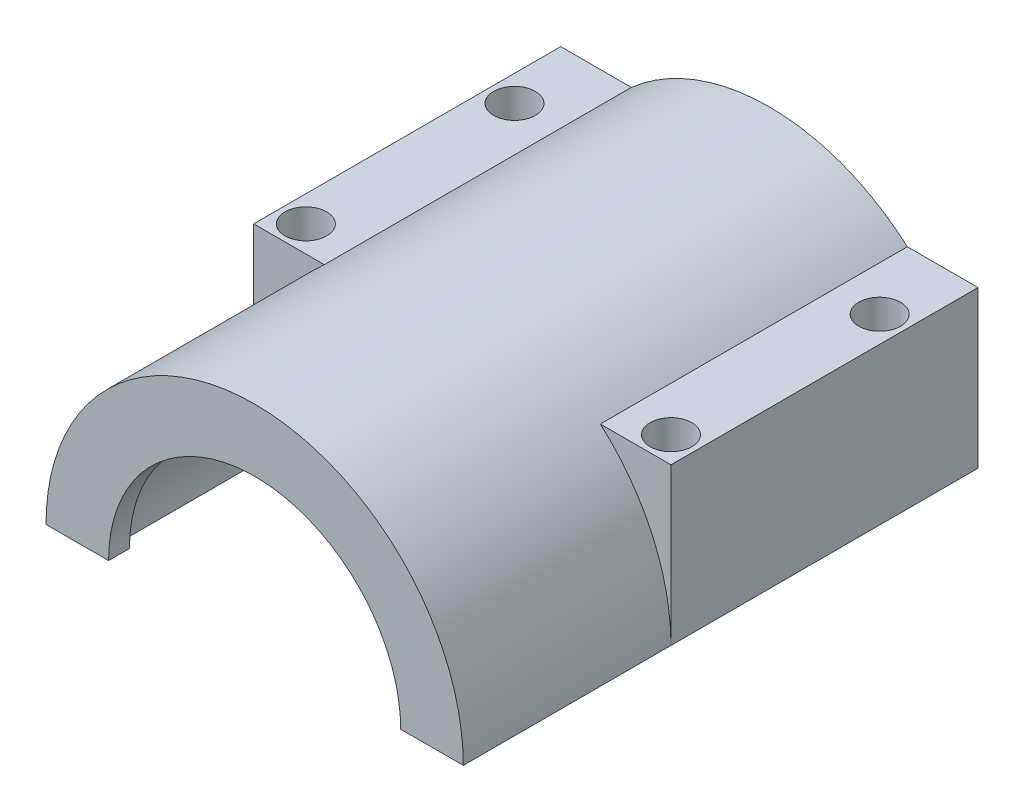
SolidWorks part; units mm, degrees
ref_plane "Front Plane" through (0, 0, 0) normal (0, 0, 1) x (1, 0, 0)
ref_plane "Top Plane" through (0, 0, 0) normal (0, 1, 0) x (1, 0, 0)
ref_plane "Right Plane" through (0, 0, 0) normal (1, 0, 0) x (0, 0, -1)
sketch "Sketch1" plane through (0, 0, 0) normal (0, 0, 1) x (1, 0, 0)
  line L0 (0, -55) -> (0, 55) construction
  line L1 (55, 0) -> (-55, 0) construction
  circle A0 centre (0, 0) radius 18.415 construction
  circle A1 centre (0, 7) radius 6 construction
  dimension "D1" = 12
  dimension "D3" = 36.83
  dimension "D2" = 7
sketch "Sketch2" plane through (0, 0, 0) normal (0, 0, 1) x (1, 0, 0)
  line L0 (-19.05, 0) -> (-25.4, 0)
  line L1 (20.2565, 0) -> (-20.2565, 0) construction
  line L2 (19.05, 0) -> (25.4, 0)
  arc A1 (19.05, 0) -> (-19.05, 0) centre (0, 0) ccw
  arc A2 (-25.4, 0) -> (25.4, 0) centre (0, 0) cw
  dimension "D1" = 38.1
  dimension "D2" = 6.35
extrude "Boss-Extrude1" add sketch "Sketch2" along normal blind 52.578
sketch "Sketch3" plane through (0, 0, 0) normal (0, 0, -1) x (-1, 0, 0)
  line L0 (-25.4, 0) -> (-13, 0)
  line L1 (0, 24.0983) -> (0, -24.0983) construction
  line L3 (-1, 0) -> (25.4, 0)
  circle A0 centre (0, 7) radius 6 construction
  arc A2 (25.4, 0) -> (-25.4, 0) centre (0, 0) ccw construction
  arc A3 (25.4, 0) -> (-25.4, 0) centre (0, 0) ccw
  arc A4 (-1, 0) -> (-13, 0) centre (-7, 0) ccw
  dimension "D1" = 7
extrude "Boss-Extrude2" add sketch "Sketch3" along normal blind 5
sketch "Sketch4" plane through (0, 0, 0) normal (0, 1, 0) x (1, 0, 0)
  line L0 (0, -24.0983) -> (0, 24.0983) construction
  line L1 (-22.225, -29.2) -> (22.225, -29.2) construction
  line L2 (-22.225, -29.2) -> (-22.225, -3.8) construction
  line L3 (-22.225, -3.8) -> (22.225, -3.8) construction
  line L4 (22.225, -29.2) -> (22.225, -3.8) construction
  line L5 (-22.225, -29.2) -> (22.225, -3.8) construction
  line L6 (-22.225, -3.8) -> (22.225, -29.2) construction
  line L7 (25.4, 5) -> (-25.4, 5) construction
  circle A0 centre (-22.225, -3.8) radius 2.54
  circle A1 centre (22.225, -3.8) radius 2.54
  circle A2 centre (22.225, -29.2) radius 2.54
  circle A3 centre (-22.225, -29.2) radius 2.54
  point P0 (0, -16.5)
  dimension "D2" = 5.08
  dimension "D3" = 25.4
  dimension "D1" = 8.8
  dimension "D4" = 44.45
extrude "Cut-Extrude1" cut sketch "Sketch4" along normal through all
sketch "Sketch5" plane through (0, 0, 0) normal (0, -1, 0) x (1, 0, 0)
  line L0 (-25.4, 52.578) -> (-25.4, -5) construction
  circle A0 centre (-22.225, 29.2) radius 2.54
  circle A1 centre (-22.225, 29.2) radius 3.175
  circle A2 centre (-22.225, 29.2) radius 2.54 construction
  circle A3 centre (-22.225, 3.8) radius 2.54
  circle A4 centre (-22.225, 3.8) radius 3.175
  circle A5 centre (22.225, 3.8) radius 2.54
  circle A6 centre (22.225, 3.8) radius 3.175
  circle A7 centre (22.225, 29.2) radius 2.54
  circle A8 centre (22.225, 29.2) radius 3.175
extrude "Boss-Extrude3" add sketch "Sketch5" against normal blind 19.05
sketch "Sketch6" plane through (0, 19.05, 0) normal (0, 1, 0) x (1, 0, 0)
  line L1 (16.51, -32.375) -> (25.4, -32.375)
  line L2 (16.51, -32.375) -> (16.51, 5)
  line L3 (16.51, 5) -> (25.4, 5)
  line L4 (25.4, -32.375) -> (25.4, 5)
  line L5 (16.51, -32.375) -> (25.4, 5) construction
  line L6 (16.51, 5) -> (25.4, -32.375) construction
  circle A0 centre (-22.225, -29.2) radius 3.175 construction
  circle A5 centre (22.225, -29.2) radius 2.54
  circle A6 centre (22.225, -3.8) radius 2.54
  circle A7 centre (22.225, -3.8) radius 2.54 construction
  point P4 (20.955, -13.6875)
  dimension "D1" = 8.89
extrude "Boss-Extrude4" add sketch "Sketch6" against normal up to surface (19.05 mm away) up to face at (0, 9.7986, 18.9297)
mirror "Mirror1" about plane through (0, 0, 0) normal (1, 0, 0) of "Boss-Extrude4"
sketch "Sketch7" plane through (0, 0, 52.578) normal (0, 0, 1) x (1, 0, 0)
  line L2 (19.05, 0) -> (25.4, 0)
  line L3 (-25.4, 0) -> (-19.05, 0)
  line L4 (19.05, 0) -> (25.4, 0)
  line L5 (-25.4, 0) -> (-19.05, 0)
  arc A2 (19.05, 0) -> (-19.05, 0) centre (0, 0) ccw
  arc A3 (25.4, 0) -> (-25.4, 0) centre (0, 0) ccw
  arc A4 (19.05, 0) -> (-19.05, 0) centre (0, 0) ccw
  arc A5 (25.4, 0) -> (-25.4, 0) centre (0, 0) ccw
  dimension "D1" = 0
extrude "Boss-Extrude5" add sketch "Sketch7" along normal blind 2.54
sketch "Sketch8" plane through (0, 0, 55.118) normal (0, 0, 1) x (1, 0, 0)
  line L0 (-17.78, 0) -> (-25.4, 0)
  line L1 (17.78, 0) -> (25.4, 0)
  arc A0 (25.4, 0) -> (-25.4, 0) centre (0, 0) ccw construction
  arc A1 (25.4, 0) -> (-25.4, 0) centre (0, 0) ccw
  arc A4 (17.78, 0) -> (-17.78, 0) centre (0, 0) ccw
  arc A5 (17.78, 0) -> (-17.78, 0) centre (0, 0) ccw
  dimension "D1" = 1.27
extrude "Boss-Extrude6" add sketch "Sketch8" along normal blind 2.54
